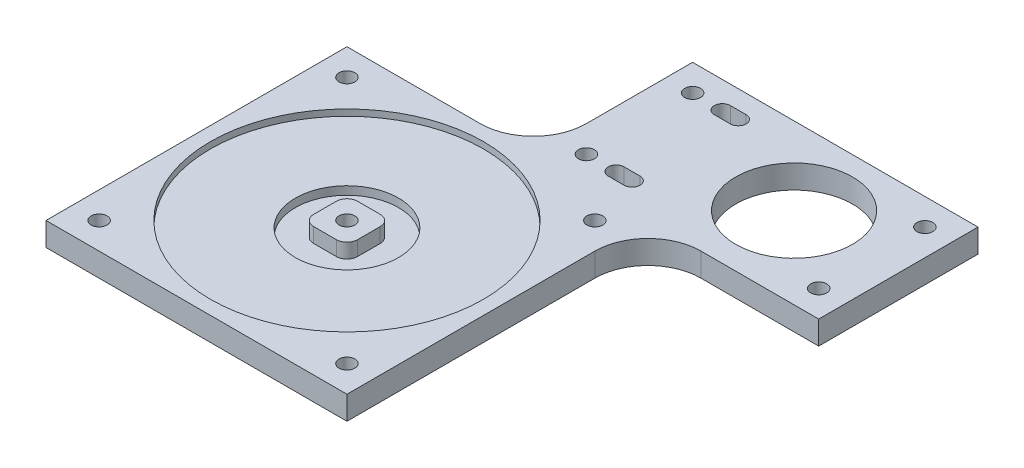
SolidWorks part; units mm, degrees
ref_plane "Front Plane" through (0, 0, 0) normal (0, 0, 1) x (1, 0, 0)
ref_plane "Top Plane" through (0, 0, 0) normal (0, 1, 0) x (1, 0, 0)
ref_plane "Right Plane" through (0, 0, 0) normal (1, 0, 0) x (0, 0, -1)
sketch "Sketch6" plane through (0, 0, 0) normal (0, 1, 0) x (1, 0, 0)
  line L10 (0, 0) -> (0, -56.68)
  line L11 (0, -56.68) -> (35.09, -56.68)
  line L14 (88.84, 0) -> (88.84, 30)
  line L19 (35.09, -56.68) -> (56.68, -56.68)
  line L20 (35.09, 0) -> (56.68, 0)
  line L21 (56.68, -56.68) -> (56.68, 0)
  line L22 (0, 0) -> (35.09, 0)
  line L23 (35.09, 0) -> (35.09, 30)
  line L24 (35.09, 30) -> (88.84, 30)
  line L25 (56.68, 0) -> (88.84, 0)
  dimension "D1" = 56.68
  dimension "D2" = 35.09
  dimension "D3" = 21.59
  dimension "D4" = 53.75
  dimension "D5" = 30
extrude "Boss-Extrude3" add sketch "Sketch6" along normal blind 4.42 contours L22 L10 L11 L19 L21 L20 region at (28.34, 0, 28.34)
extrude "Boss-Extrude4" add sketch "Sketch6<7>" along normal blind 4.42 contours L20 L25 L14 L24 L23 region at (61.965, 0, -15)
sketch "Sketch6<7>" plane through (0, 0, 0) normal (0, 1, 0) x (1, 0, 0) same geometry as "Sketch6"
sketch "Sketch7" plane through (0, 4.42, 0) normal (0, 1, 0) x (1, 0, 0)
  line L0 (0, -28.34) -> (56.68, -28.34) construction
  line L1 (0, 0) -> (0, -56.68) construction
  line L2 (56.68, -56.68) -> (56.68, 0) construction
  line L3 (28.34, -56.68) -> (28.34, 0) construction
  line L4 (0, -56.68) -> (56.68, -56.68) construction
  line L5 (0, 0) -> (35.09, 0) construction
  line L7 (28.34, -28.34) -> (32.47, -28.34)
  line L8 (28.34, -28.34) -> (28.34, -32.47)
  line L9 (28.34, -32.47) -> (32.47, -32.47)
  line L10 (32.47, -28.34) -> (32.47, -32.47)
  line L11 (28.34, -28.34) -> (32.47, -28.34)
  line L12 (28.34, -28.34) -> (28.34, -24.21)
  line L13 (28.34, -24.21) -> (32.47, -24.21)
  line L14 (32.47, -28.34) -> (32.47, -24.21)
  line L15 (28.34, -28.34) -> (24.21, -28.34)
  line L16 (28.34, -28.34) -> (28.34, -24.21)
  line L17 (28.34, -24.21) -> (24.21, -24.21)
  line L18 (24.21, -28.34) -> (24.21, -24.21)
  line L19 (28.34, -28.34) -> (24.21, -28.34)
  line L20 (28.34, -28.34) -> (28.34, -32.47)
  line L21 (28.34, -32.47) -> (24.21, -32.47)
  line L22 (24.21, -28.34) -> (24.21, -32.47)
  circle A0 centre (28.34, -28.34) radius 9.715
  circle A1 centre (28.34, -28.34) radius 16.51
  circle A2 centre (28.34, -28.34) radius 25.72
  dimension "D2" = 19.43
  dimension "D3" = 33.02
  dimension "D4" = 51.44
  dimension "D1" = 4.13
extrude "Boss-Extrude5" add sketch "Sketch7" along normal blind 0.7 contours L15 L22 L21 L8 | L18 L15 L12 L17 | L7 L14 L13 L12 | L10 L7 L8 L9 region at (30.405, 4.42, 26.275) region at (30.405, 4.42, 30.405) region at (26.275, 4.42, 26.275) region at (26.275, 4.42, 30.405)
extrude "Cut-Extrude1" cut sketch "Sketch7<3>" against normal blind 1.2 contours A2 A1 | A1 A0 region at (12.297, 4.42, 28.34) region at (3.3475, 4.42, 28.34)
sketch "Sketch7<3>" plane through (0, 4.42, 0) normal (0, 1, 0) x (1, 0, 0) same geometry as "Sketch7"
extrude "Cut-Extrude2" cut sketch "Sketch7<4>" against normal blind 2.76 contours A0 L22 L18 L17 L13 L14 L10 L9 L21 region at (18.8998, 4.42, 28.34)
sketch "Sketch7<4>" plane through (0, 4.42, 0) normal (0, 1, 0) x (1, 0, 0) same geometry as "Sketch7"
fillet "Fillet2" radius 2 4 edges at (32.47, 3.39, 24.21) (24.21, 3.39, 24.21) (32.47, 3.39, 32.47) (24.21, 3.39, 32.47)
sketch "Sketch8" plane through (0, 5.12, 0) normal (0, 1, 0) x (1, 0, 0)
  circle A0 centre (28.34, -28.34) radius 1.5
  dimension "D1" = 3
extrude "Cut-Extrude3" cut sketch "Sketch8" against normal through all
sketch "Sketch9" plane through (0, 4.42, 0) normal (0, 1, 0) x (1, 0, 0)
  line L0 (0, 0) -> (35.09, 0) construction
  line L1 (0, 0) -> (0, -56.68) construction
  line L2 (56.68, -56.68) -> (56.68, 0) construction
  line L3 (56.68, 0) -> (88.84, 0) construction
  line L4 (0, -56.68) -> (56.68, -56.68) construction
  circle A0 centre (5, -5) radius 1.5
  circle A1 centre (51.68, -5) radius 1.5
  circle A2 centre (51.68, -51.68) radius 1.5
  circle A3 centre (5, -51.68) radius 1.5
  dimension "D3" = 3
  dimension "D6" = 3
  dimension "D8" = 3
  dimension "D12" = 3
  dimension "D1" = 5
  dimension "D2" = 5
  dimension "D4" = 5
  dimension "D5" = 5
  dimension "D7" = 5
  dimension "D9" = 5
  dimension "D10" = 5
  dimension "D11" = 5
extrude "Cut-Extrude4" cut sketch "Sketch9" against normal through all
sketch "Sketch10" plane through (0, 4.42, 0) normal (0, 1, 0) x (1, 0, 0)
  line L0 (35.09, 0) -> (35.09, 30) construction
  line L1 (35.09, 30) -> (88.84, 30) construction
  line L2 (88.84, 0) -> (88.84, 30) construction
  line L3 (45.69, 26.5) -> (48.69, 26.5)
  line L4 (45.69, 23.5) -> (48.69, 23.5)
  line L5 (56.68, 0) -> (88.84, 0) construction
  line L6 (0, 0) -> (35.09, 0) construction
  line L8 (45.69, 6.5) -> (48.69, 6.5)
  line L9 (45.69, 3.5) -> (48.69, 3.5)
  circle A0 centre (40.09, 25) radius 1.5
  circle A1 centre (40.09, 5) radius 1.5
  circle A2 centre (83.84, 5) radius 1.5
  circle A3 centre (83.84, 25) radius 1.5
  arc A4 (45.69, 26.5) -> (45.69, 23.5) centre (45.69, 25) ccw
  arc A5 (48.69, 23.5) -> (48.69, 26.5) centre (48.69, 25) ccw
  arc A6 (45.69, 6.5) -> (45.69, 3.5) centre (45.69, 5) ccw
  arc A7 (48.69, 3.5) -> (48.69, 6.5) centre (48.69, 5) ccw
  dimension "D1" = 3
  dimension "D2" = 3
  dimension "D3" = 3
  dimension "D4" = 3
  dimension "D5" = 3
  dimension "D6" = 3
  dimension "D7" = 3
  dimension "D8" = 3
  dimension "D9" = 5
  dimension "D10" = 5
  dimension "D11" = 5
  dimension "D12" = 5
  dimension "D13" = 5
  dimension "D14" = 38.15
  dimension "D15" = 5
  dimension "D16" = 35.15
  dimension "D17" = 5
  dimension "D18" = 5
  dimension "D19" = 5
  dimension "D20" = 38.15
  dimension "D21" = 5
  dimension "D22" = 35.15
  dimension "D23" = 5
  dimension "D24" = 5
extrude "Cut-Extrude5" cut sketch "Sketch10" against normal through all
sketch "Sketch11" plane through (0, 4.42, 0) normal (0, 1, 0) x (1, 0, 0)
  line L0 (88.84, 0) -> (88.84, 30) construction
  line L1 (74.9772, 24.4937) -> (75.4014, 25.2325)
  line L3 (64.051, 5.4621) -> (63.6268, 4.7232)
  line L5 (73.629, 5.4621) -> (74.0532, 4.7232)
  line L6 (62.7028, 24.4937) -> (62.2786, 25.2325)
  circle A0 centre (68.84, 15.3649) radius 11
  circle A1 centre (68.84, 15.3649) radius 11.85
  dimension "D1" = 22
  dimension "D3" = 23.7
  dimension "D2" = 20
extrude "Cut-Extrude6" cut sketch "Sketch11" against normal through all contours A0 region at (68.84, 4.42, -15.3649)
fillet "Fillet7" radius 10 2 edges at (56.68, 2.21, 0) (35.09, 2.21, 0)
sketch "Sketch12" plane through (0, 5.12, 0) normal (0, 1, 0) x (1, 0, 0)
  line L0 (30.47, -24.21) -> (26.21, -24.21) construction
  line L1 (24.21, -24.21) -> (32.47, -24.21)
  line L2 (24.21, -24.21) -> (24.21, -32.47)
  line L3 (24.21, -32.47) -> (32.47, -32.47)
  line L4 (32.47, -24.21) -> (32.47, -32.47)
  line L5 (24.21, -26.21) -> (24.21, -30.47) construction
  line L6 (30.47, -32.47) -> (26.21, -32.47) construction
  line L7 (32.47, -26.21) -> (32.47, -30.47) construction
extrude "Cut-Extrude7" cut sketch "Sketch12" against normal up to surface (0.7 mm away) up to face at (68.84, 4.42, -4.3649)
